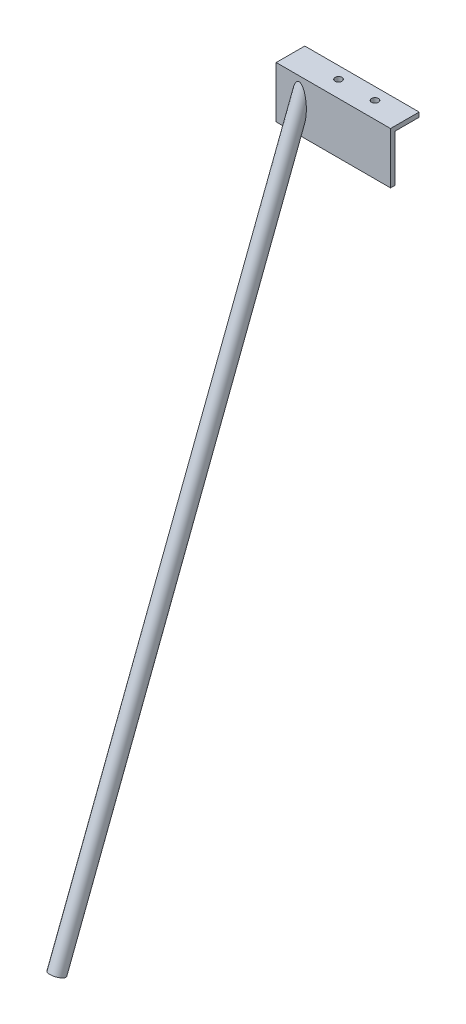
SolidWorks part; units mm, degrees
ref_plane "Front Plane" through (0, 0, 0) normal (0, 0, 1) x (1, 0, 0)
ref_plane "Top Plane" through (0, 0, 0) normal (0, 1, 0) x (1, 0, 0)
ref_plane "Right Plane" through (0, 0, 0) normal (1, 0, 0) x (0, 0, -1)
sketch "Sketch1" plane through (0, 0, 0) normal (1, 0, 0) x (0, 0, -1)
  line L0 (0, 0) -> (25, 0)
  line L1 (25, 0) -> (25, -4)
  line L2 (25, -4) -> (4, -4)
  line L3 (4, -4) -> (4, -45)
  line L4 (4, -45) -> (0, -45)
  line L5 (0, -45) -> (0, 0)
  dimension "D1" = 25
  dimension "D2" = 4
  dimension "D3" = 45
  dimension "D4" = 4
extrude "Boss-Extrude1" add sketch "Sketch1" along normal blind 100
ref_plane "Plane1" through (0, -39.2208, 15.0554) normal (0, 0.9336, -0.3584) x (-1, 0, 0)
sketch "Sketch2" plane through (0, -39.2208, 15.0554) normal (0, 0.9336, -0.3584) x (-1, 0, 0)
  line L3 (0, 0) -> (-20, 0) construction
  circle A0 centre (-20, -8) radius 6.375
  circle A1 centre (-20, -8) radius 4.9
  point P3 (0, 0)
  point P4 (0, 0)
  point P8 (0, 0)
  point P9 (-20, -4.666)
  dimension "D1" = 12.75
  dimension "D2" = 9.8
  dimension "D3" = 20
  dimension "D4" = 8
extrude "Boss-Extrude2" add sketch "Sketch2" along normal up to surface and the other way blind 570 up to face at (50, -22.5, 0)
hole_wizard "Ø6.0mm Dowel Hole1" positions "Sketch3" profile "Sketch4" hole size "Ø6.0" standard "ISO" end condition through all
sketch "Sketch3" plane through (0, 0, 0) normal (0, 1, 0) x (1, 0, 0)
  line L1 (100, 25) -> (0, 25) construction
  line L3 (0, 25) -> (0, 0) construction
  point P0 (40, 14.5)
  point P2 (71.89, 14.5)
  point P17 (0, 0)
  dimension "D1" = 10.5
  dimension "D2" = 40
  dimension "D3" = 31.89
sketch "Sketch4" plane through (40, 0, -14.5) normal (1, 0, 0) x (0, 0, 1)
  line L0 (0, 0) -> (0, 576.5131)
  line L1 (0, 576.5131) -> (3, 576.5131)
  line L2 (3, 576.5131) -> (3, 0)
  line L5 (3, 0) -> (0, 0)
  line L11 (0, -6.35) -> (0, 107.95) construction
  dimension "Thru Hole Dia." = 6
  dimension "Thru Hole Depth" = 576.5131
equation "\"D4@Sketch1\"=\"D2@Sketch1\""
